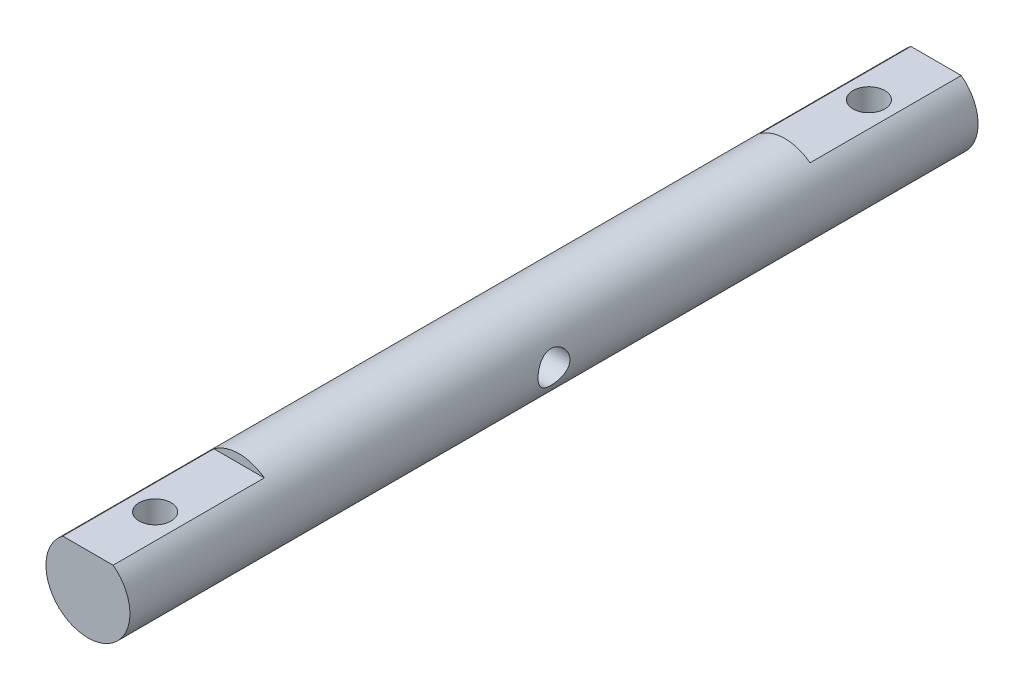
SolidWorks part; units mm, degrees
material "7050-T73510"
ref_plane "前视基准面" through (0, 0, 0) normal (0, 0, 1) x (1, 0, 0)
ref_plane "上视基准面" through (0, 0, 0) normal (0, 1, 0) x (1, 0, 0)
ref_plane "右视基准面" through (0, 0, 0) normal (1, 0, 0) x (0, 0, -1)
sketch "草图1" plane through (0, 0, 0) normal (0, 0, 1) x (1, 0, 0)
  circle A0 centre (0, 0) radius 5
  dimension "D1" = 10
extrude "凸台-拉伸1" add sketch "草图1" along normal mid plane 101
sketch "草图2" plane through (0, 0, 0) normal (0, 1, 0) x (1, 0, 0)
  line L0 (-5, -50.5) -> (5, -50.5) construction
  line L1 (5, 50.5) -> (-5, 50.5) construction
  circle A0 centre (0, 0) radius 1.9
  circle A1 centre (0, 42.5) radius 1.9
  circle A2 centre (0, -42.5) radius 1.9
  dimension "D1" = 3.8
  dimension "D2" = 8
  dimension "D3" = 8
extrude "切除-拉伸1" cut sketch "草图2" against normal mid plane 70
ref_plane "基准面1" through (0, 4, 0) normal (0, 1, 0) x (1, 0, 0)
sketch "草图4" plane through (0, 4, 0) normal (0, 1, 0) x (1, 0, 0)
  line L1 (-9.6511, 32.5) -> (9.6511, 32.5)
  line L2 (-9.6511, 32.5) -> (-9.6511, 52.5)
  line L3 (-9.6511, 52.5) -> (9.6511, 52.5)
  line L4 (9.6511, 32.5) -> (9.6511, 52.5)
  line L5 (-9.6511, 32.5) -> (9.6511, 52.5) construction
  line L6 (-9.6511, 52.5) -> (9.6511, 32.5) construction
  line L7 (-19.8649, -52.5) -> (19.8649, -52.5)
  line L8 (-19.8649, -52.5) -> (-19.8649, -32.5)
  line L9 (-19.8649, -32.5) -> (19.8649, -32.5)
  line L10 (19.8649, -52.5) -> (19.8649, -32.5)
  line L11 (-19.8649, -52.5) -> (19.8649, -32.5) construction
  line L12 (-19.8649, -32.5) -> (19.8649, -52.5) construction
  point P0 (0, 42.5)
  point P6 (0, -42.5)
  dimension "D1" = 20
  dimension "D2" = 20
extrude "切除-拉伸2" cut sketch "草图4" along normal blind 36
sketch "草图5" plane through (0, 0, 0) normal (0, 1, 0) x (1, 0, 0)
  circle A0 centre (0, 0) radius 1.9 construction
  circle A1 centre (0, 0) radius 1.9
extrude "凸台-拉伸2" add sketch "草图5" along normal up to surface (5 mm away) up to face at (-0.2905, -4.9916, 40.6223)
sketch "草图6" plane through (0, 0, 0) normal (0, -1, 0) x (1, 0, 0)
  circle A1 centre (0, 0) radius 1.9
  circle A2 centre (0, 0) radius 1.9
  dimension "D1" = 0
extrude "凸台-拉伸3" add sketch "草图6" along normal up to surface (5 mm away) up to face at (-0.2905, -4.9916, 40.6223)
sketch "草图7" plane through (0, 0, 0) normal (1, 0, 0) x (0, 0, -1)
  circle A0 centre (0, 0) radius 1.9
  dimension "D1" = 3.8
extrude "切除-拉伸3" cut sketch "草图7" against normal mid plane 36
